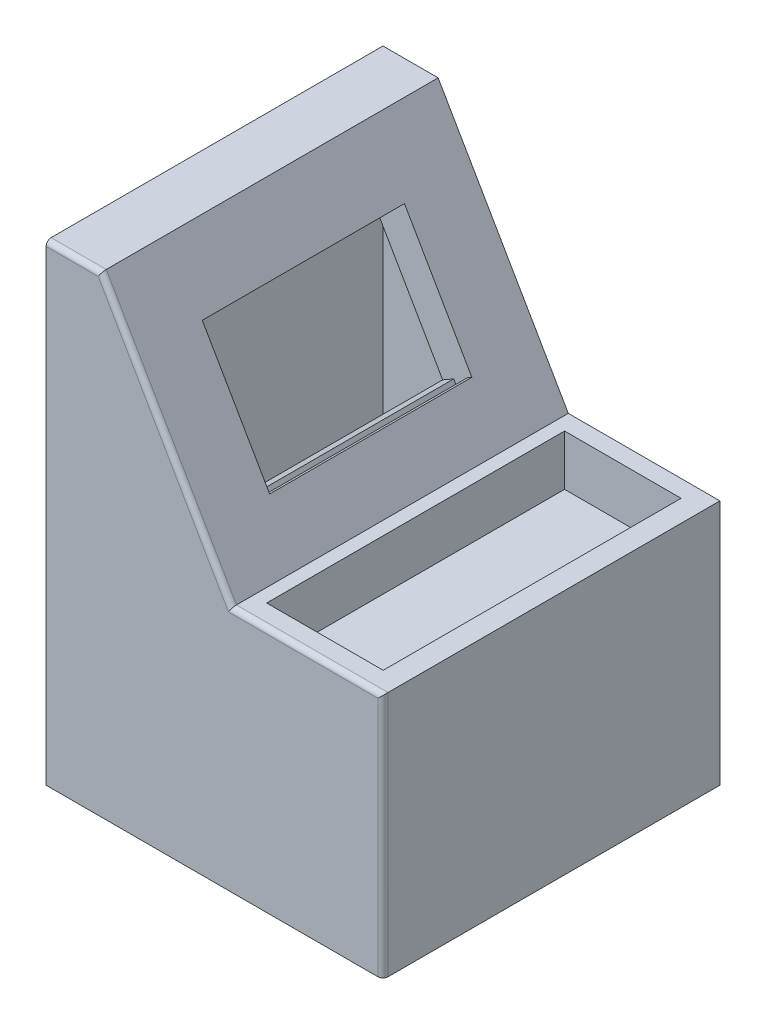
SolidWorks part; units mm, degrees
ref_plane "Front Plane" through (0, 0, 0) normal (0, 0, 1) x (1, 0, 0)
ref_plane "Top Plane" through (0, 0, 0) normal (0, 1, 0) x (1, 0, 0)
ref_plane "Right Plane" through (0, 0, 0) normal (1, 0, 0) x (0, 0, -1)
sketch "Sketch1" plane through (0, 0, 0) normal (0, 0, 1) x (1, 0, 0)
  line L0 (0, 203.2) -> (0, 711.2)
  line L1 (0, 0) -> (508, 0)
  line L2 (0, 0) -> (0, 203.2)
  line L3 (0, 203.2) -> (508, 203.2)
  line L4 (508, 0) -> (508, 203.2)
  line L5 (0, 711.2) -> (83.1288, 711.2)
  line L6 (83.1288, 711.2) -> (279.4, 371.2483)
  line L7 (279.4, 371.2483) -> (508, 371.2483)
  line L8 (508, 371.2483) -> (508, 203.2)
  dimension "D1" = 508
  dimension "D2" = 508
  dimension "D3" = 203.2
  dimension "D4" = 120
  dimension "D5" = 392.5424
  dimension "D6" = 228.6
extrude "Boss-Extrude1" add sketch "Sketch1" along normal blind 508 contours L8 L7 L6 L5 L0 L3 | L2 L1 L4 L3 region at (189.225, 380.8468, 0)
sketch "Sketch2" plane through (0, 371.2483, 0) normal (0, 1, 0) x (1, 0, 0)
  line L1 (299.6447, -25.9057) -> (475.366, -25.9057)
  line L2 (299.6447, -25.9057) -> (299.6447, -475.0665)
  line L3 (299.6447, -475.0665) -> (475.366, -475.0665)
  line L4 (475.366, -25.9057) -> (475.366, -475.0665)
extrude "Cut-Extrude1" cut sketch "Sketch2" against normal blind 76.2
sketch "Sketch3" plane through (370.3053, 213.7958, 0) normal (0.866, 0.5, 0) x (0, 0, -1)
  line L0 (0, 574.3529) -> (0, 181.8105) construction
  line L1 (-406.4, 472.7529) -> (-101.6, 472.7529)
  line L2 (-406.4, 472.7529) -> (-406.4, 269.5529)
  line L3 (-406.4, 269.5529) -> (-101.6, 269.5529)
  line L4 (-101.6, 472.7529) -> (-101.6, 269.5529)
  line L7 (-508, 574.3529) -> (0, 574.3529) construction
  dimension "D1" = 203.2
  dimension "D2" = 304.8
  dimension "D3" = 101.6
  dimension "D4" = 101.6
extrude "Cut-Extrude3" cut sketch "Sketch3" against normal blind 50.8
shell "Shell2" thickness 27.94 removed face at (140.7347, 509.8236, 254)
fillet "Fillet1" radius 7.62 4 edges at (41.5644, 711.2, 508) (181.2644, 541.2242, 508) (393.7, 371.2483, 508) (508, 185.6242, 508)
sketch "Sketch6" plane through (0, 0, 406.4) normal (0, 0, -1) x (-1, 0, 0)
  line L0 (-109.7118, 652.4423) -> (-240.0209, 424.215)
  line L1 (-275.0006, 363.6283) -> (-78.7294, 703.58) construction
  line L2 (-240.0209, 424.215) -> (-218.4495, 411.8986)
  line L3 (-218.4495, 411.8986) -> (-97.8271, 645.6566)
  line L4 (-97.8271, 645.6566) -> (-109.7118, 652.4423)
extrude "Cut-Extrude4" cut sketch "Sketch6" along normal up to surface (304.8 mm away) and the other way blind 97.536 up to face at (162.7318, 522.5236, 101.6)
ref_plane "Plane1" through (135.8523, 0, 0) normal (-1, 0, 0) x (0, 0, 1)
